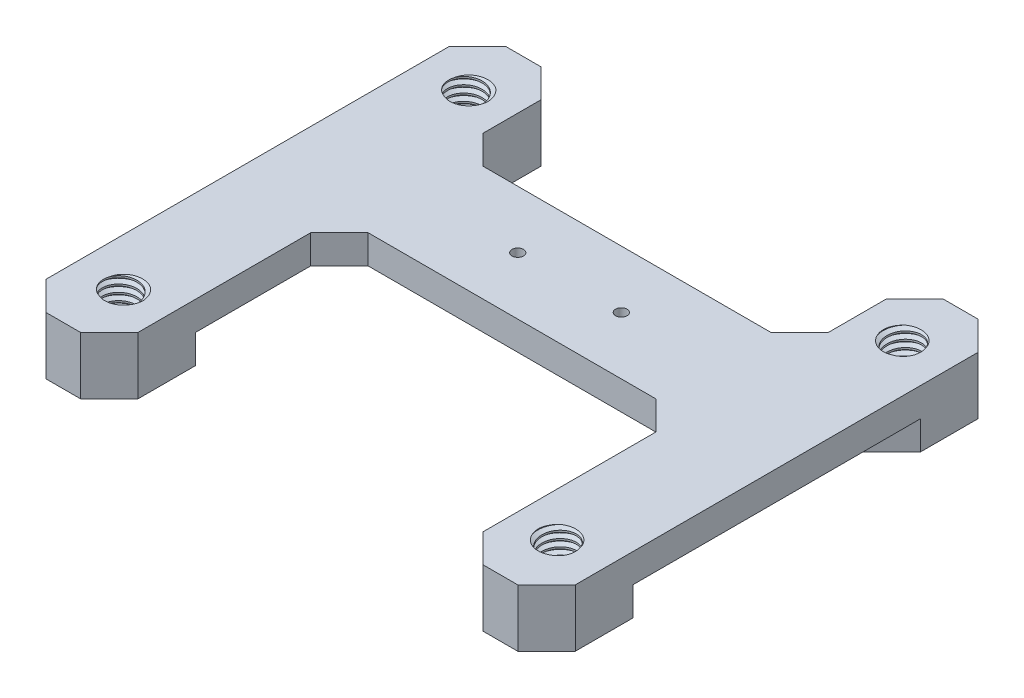
SolidWorks part; units mm, degrees
ref_plane "Front Plane" through (0, 0, 0) normal (0, 0, 1) x (1, 0, 0)
ref_plane "Top Plane" through (0, 0, 0) normal (0, 1, 0) x (1, 0, 0)
ref_plane "Right Plane" through (0, 0, 0) normal (1, 0, 0) x (0, 0, -1)
sketch "Sketch1" plane through (0, 0, 0) normal (0, 1, 0) x (1, 0, 0)
  line L1 (-30, -10) -> (30, -10)
  line L2 (-30, -10) -> (-30, 10)
  line L3 (-30, 10) -> (30, 10)
  line L4 (30, -10) -> (30, 10)
  line L5 (-30, -10) -> (30, 10) construction
  line L6 (-30, 10) -> (30, -10) construction
  point P0 (0, 0)
  dimension "D1" = 60
  dimension "D2" = 20
extrude "Boss-Extrude1" add sketch "Sketch1" against normal blind 5
sketch "Sketch2" plane through (0, 0, 0) normal (0, 1, 0) x (1, 0, 0)
  line L0 (-30, 10) -> (-30, -10) construction
  line L1 (-30, 30) -> (-46, 30)
  line L2 (-30, 30) -> (-30, -50)
  line L3 (-30, -50) -> (-46, -50)
  line L4 (-46, 30) -> (-46, -50)
  line L5 (-46, 30) -> (-30, -50) construction
  circle A0 centre (-38, 20) radius 3
  circle A1 centre (-38, -40) radius 3
  point P10 (-38, -10)
  point P11 (0, 0)
  dimension "D6" = 6
  dimension "D7" = 6
  dimension "D1" = 10
  dimension "D2" = 10
  dimension "D3" = 10
  dimension "D4" = 80
  dimension "D5" = 16
extrude "Boss-Extrude2" add sketch "Sketch2" against normal blind 10
sketch "Sketch3" plane through (0, -10, 0) normal (0, -1, 0) x (1, 0, 0)
  line L0 (-46, -30) -> (-46, 50) construction
  line L1 (-46, 30) -> (-30, 30)
  line L2 (-46, 30) -> (-46, -10)
  line L3 (-46, -10) -> (-30, -10)
  line L4 (-30, 30) -> (-30, -10)
  line L5 (-30, 50) -> (-30, -30) construction
  circle A0 centre (-38, -20) radius 3 construction
  circle A1 centre (-38, 40) radius 3 construction
  dimension "D1" = 10
  dimension "D2" = 10
extrude "Cut-Extrude1" cut sketch "Sketch3" against normal blind 5
thread "Thread1" pitch 1.25 start angle 0, offset 1, length 0, pitch 1.25, diameter 6
ref_plane "Plane1" through (-41, 1, 40) normal (0, 0, 1) x (-1, 0, 0)
sketch "Thread Profile1" plane through (-41, 1, 40) normal (0, 0, 1) x (-1, 0, 0)
  line L0 (0, 0) -> (0, 1.25) construction
  line L1 (0, 0) -> (0.6766, 0.3906)
  line L2 (0.6766, 0.3906) -> (0.6766, 0.5469)
  line L3 (0.6766, 0.5469) -> (0, 0.9375)
  line L4 (0.6766, 0.4687) -> (0, 0.4687) construction
  line L11 (0, 0) -> (0, 0.9375)
  point P2 (0, 0)
  dimension "Pitch" = 1.25
  dimension "Profile_Angle" = 60
  dimension "Profile_Land" = 0.1562
  dimension "Profile_Height" = 0.6766
pattern_linear "LPattern1" count 2 spacing 60 along (0, 0, -1) of "Thread1"
chamfer "Chamfer1" distance 5 angle 45 9 edges at (-46, -7.5, -10) (-46, -7.5, 30) (-30, -7.5, 30) (-30, -2.5, -10) (-30, -2.5, 10) (-46, -5, 50) (-30, -5, 50) (-30, -5, -30) (-46, -5, -30)
chamfer "Chamfer2" distance 5 angle 45 1 edges at (-30, -7.5, -10)
mirror "Mirror1" about plane through (0, 0, 0) normal (1, 0, 0) of "Chamfer2", "Chamfer1", "Boss-Extrude2", "Cut-Extrude1", "Thread1", "LPattern1"
sketch "Sketch8" plane through (0, 0, 0) normal (0, 1, 0) x (1, 0, 0)
  line L0 (9, 0) -> (-9, 0) construction
  circle A0 centre (9, 0) radius 1
  circle A1 centre (-9, 0) radius 1
  point P4 (0, 0)
  dimension "D1" = 2
  dimension "D2" = 18
extrude "Cut-Extrude2" cut sketch "Sketch8" against normal blind 5
